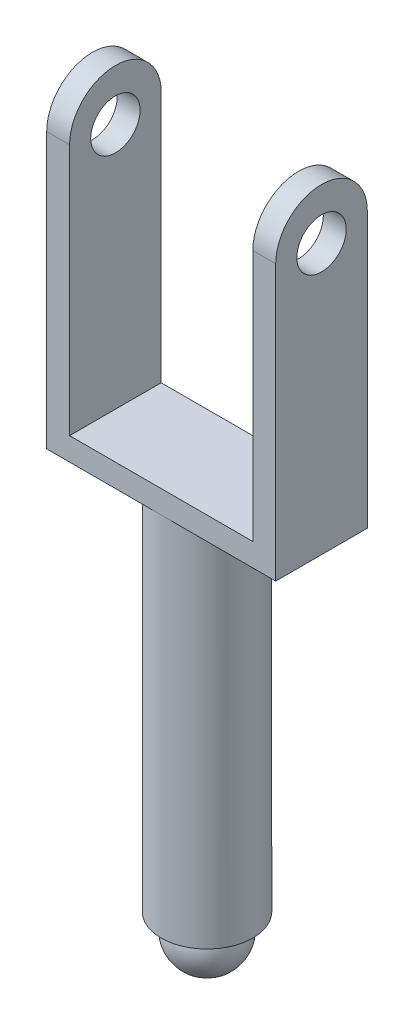
SolidWorks part; units mm, degrees
ref_plane "前视基准面" through (0, 0, 0) normal (0, 0, 1) x (1, 0, 0)
ref_plane "上视基准面" through (0, 0, 0) normal (0, 1, 0) x (1, 0, 0)
ref_plane "右视基准面" through (0, 0, 0) normal (1, 0, 0) x (0, 0, -1)
sketch "草图1" plane through (0, 0, 0) normal (0, 1, 0) x (1, 0, 0)
  circle A0 centre (0, 0) radius 7.5
  circle A1 centre (0, 0) radius 10
  dimension "D1" = 15
  dimension "D2" = 20
extrude "凸台-拉伸1" add sketch "草图1" along normal blind 80
sketch "草图2" plane through (0, 80, 0) normal (0, 1, 0) x (1, 0, 0)
  line L1 (-25, 10) -> (25, 10)
  line L2 (-25, 10) -> (-25, -10)
  line L3 (-25, -10) -> (25, -10)
  line L4 (25, 10) -> (25, -10)
  line L5 (-25, 10) -> (25, -10) construction
  line L6 (-25, -10) -> (25, 10) construction
  circle A0 centre (0, 0) radius 10 construction
  point P0 (0, 0)
  dimension "D1" = 50
extrude "凸台-拉伸2" add sketch "草图2" along normal blind 70
sketch "草图3" plane through (0, 150, 0) normal (0, 1, 0) x (1, 0, 0)
  line L0 (25, 10) -> (-25, 10) construction
  line L1 (-20, 10) -> (20, 10)
  line L2 (-20, 10) -> (-20, -10)
  line L3 (-20, -10) -> (20, -10)
  line L4 (20, 10) -> (20, -10)
  line L5 (-25, -10) -> (25, -10) construction
  line L6 (-25, 10) -> (-25, -10) construction
  line L7 (25, -10) -> (25, 10) construction
  dimension "D1" = 5
  dimension "D2" = 5
extrude "切除-拉伸1" cut sketch "草图3" against normal blind 65
sketch "草图4" plane through (-25, 0, 0) normal (-1, 0, 0) x (0, 0, 1)
  circle A0 centre (0, 138.8582) radius 5.3938
  point P2 (0, 138.8582)
extrude "切除-拉伸2" cut sketch "草图4" against normal through all
fillet "圆角1" 2 edges at (-22.5, 150, 10) (-22.5, 150, -10) type full round first side face at (0, 112.2222, 10) second side face at (0, 112.2222, -10) middle face at (-22.5, 150, 0)
fillet "圆角2" 2 edges at (22.5, 150, 10) (22.5, 150, -10) type full round first side face at (0, 110, 10) second side face at (0, 110, -10) middle face at (22.5, 150, 0)
sketch "草图5" plane through (0, 80, 0) normal (0, -1, 0) x (1, 0, 0)
  circle A1 centre (0, 0) radius 7.5
  circle A2 centre (0, 0) radius 7.5
  dimension "D1" = 0
extrude "凸台-拉伸3" add sketch "草图5" along normal up to surface (80 mm away) up to face at (0, 0, 10)
sketch "草图6" plane through (0, 0, 0) normal (0, 0, 1) x (1, 0, 0)
  line L0 (0, 4.1116) -> (0, -10.8884)
  arc A0 (0, -10.8884) -> (0, 4.1116) centre (0, -3.3884) ccw
  point P1 (0.0202, -2.7295)
  point P4 (0, 0)
  point P5 (0, -4.1649)
  point P7 (0, -2.8252)
  point P8 (0, -1.6769)
  point P9 (0, -3.3884)
  dimension "D1" = 15
revolve "旋转1" add sketch "草图6" angle 360 about L0
